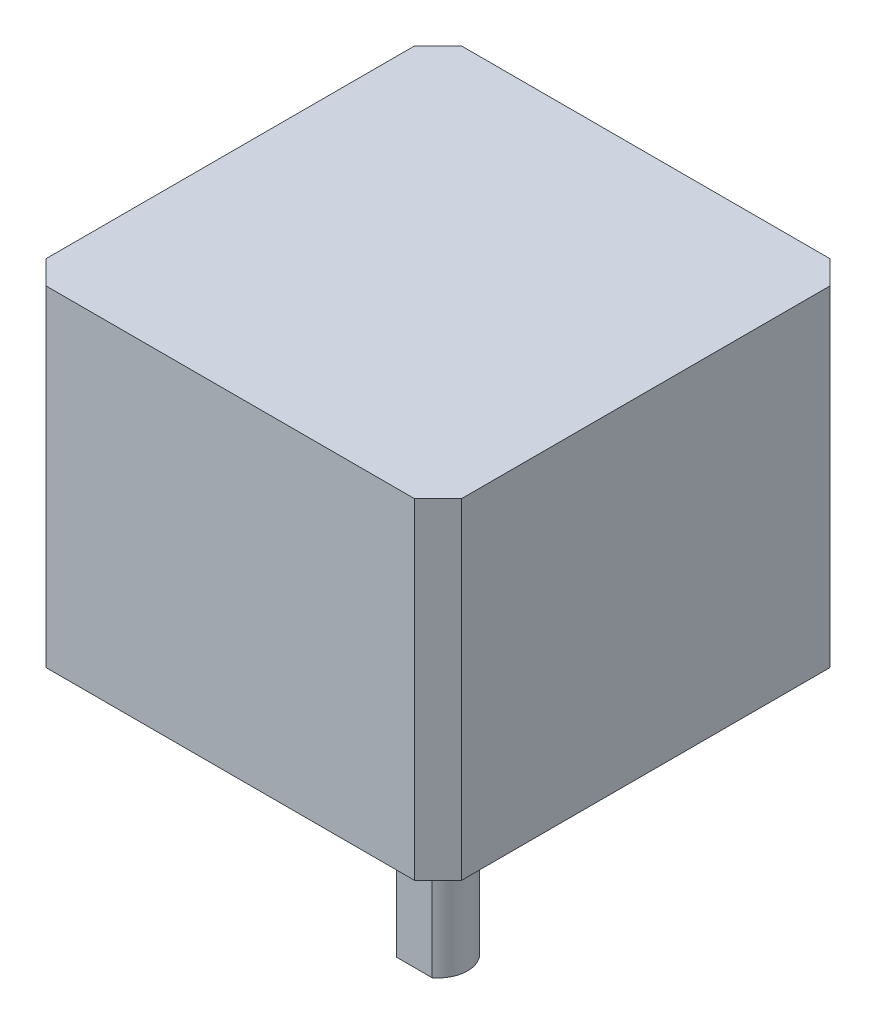
SolidWorks part; units mm, degrees
ref_plane "Front Plane" through (0, 0, 0) normal (0, 0, 1) x (1, 0, 0)
ref_plane "Top Plane" through (0, 0, 0) normal (0, 1, 0) x (1, 0, 0)
ref_plane "Right Plane" through (0, 0, 0) normal (1, 0, 0) x (0, 0, -1)
sketch "Sketch1" plane through (0, 0, 0) normal (0, 1, 0) x (1, 0, 0)
  line L1 (-17.6, 17.6) -> (17.6, 17.6)
  line L2 (-17.6, 17.6) -> (-17.6, -17.6)
  line L3 (-17.6, -17.6) -> (17.6, -17.6)
  line L4 (17.6, 17.6) -> (17.6, -17.6)
extrude "Boss-Extrude1" add sketch "Sketch1" along normal blind 28
sketch "Sketch2" plane through (0, 0, 0) normal (0, -1, 0) x (1, 0, 0)
  circle A0 centre (0, 0) radius 11
extrude "Boss-Extrude2" add sketch "Sketch2" along normal blind 2
sketch "Sketch3" plane through (0, -2, 0) normal (0, -1, 0) x (1, 0, 0)
  circle A0 centre (0, 0) radius 2.5
extrude "Boss-Extrude3" add sketch "Sketch3" along normal blind 9
sketch "Sketch4" plane through (0, 0, 0) normal (0, 1, 0) x (1, 0, 0)
  line L1 (-1.5, -2) -> (1.5, -2)
  arc A0 (1.5, -2) -> (-1.5, -2) centre (0, 0) ccw
extrude "Boss-Extrude4" add sketch "Sketch4" against normal blind 22
fillet "Chamfer8" radius 2 1 edges at (-17.6, 14, 17.6) type face fillet profile chamfer first side face at (0, 14, 17.6) second side face at (-17.6, 14, 0)
fillet "Chamfer9" radius 2 1 edges at (17.6, 14, 17.6) type face fillet profile chamfer first side face at (17.6, 14, 0) second side face at (1, 14, 17.6)
fillet "Chamfer10" radius 2 1 edges at (17.6, 14, -17.6) type face fillet profile chamfer first side face at (17.6, 14, -1) second side face at (0, 14, -17.6)
fillet "Chamfer11" radius 2 1 edges at (-17.6, 14, -17.6) type face fillet profile chamfer first side face at (-17.6, 14, -1) second side face at (-1, 14, -17.6)
sketch "Sketch6" plane through (0, 0, 0) normal (0, -1, 0) x (1, 0, 0)
  circle A0 centre (13, 13) radius 1.5
  circle A1 centre (13, -13) radius 1.5
  circle A2 centre (-13, -13) radius 1.5
  circle A3 centre (-13, 13) radius 1.5
  point P10 (0, 0)
  dimension "D1" = 4
extrude "Cut-Extrude1" cut sketch "Sketch6" against normal blind 4
